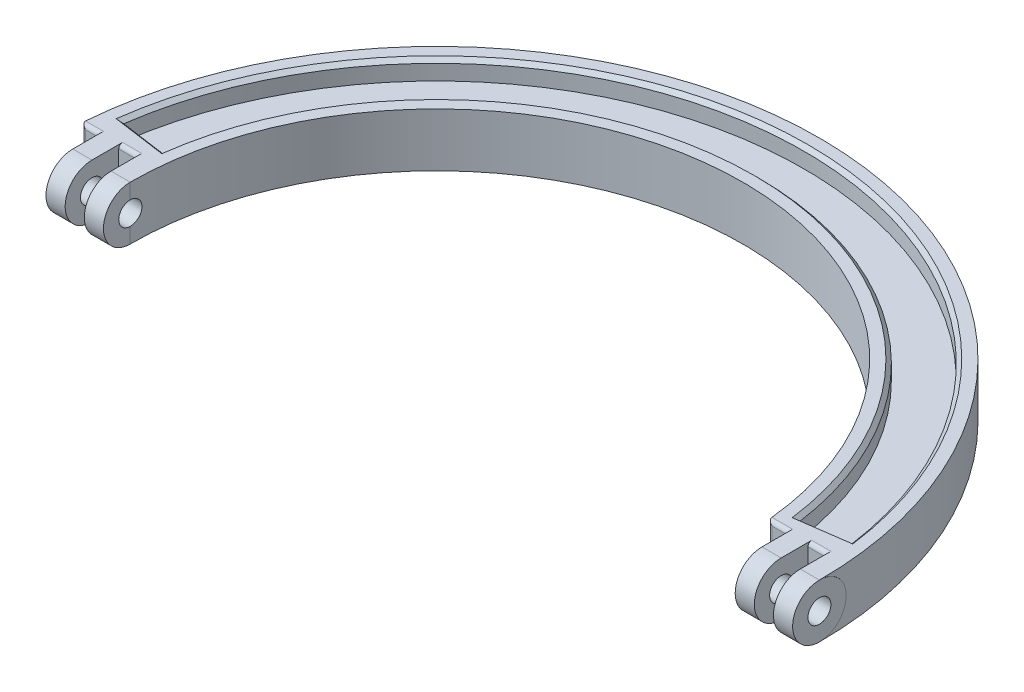
SolidWorks part; units mm, degrees
ref_plane "前视基准面" through (0, 0, 0) normal (0, 0, 1) x (1, 0, 0)
ref_plane "上视基准面" through (0, 0, 0) normal (0, 1, 0) x (1, 0, 0)
ref_plane "右视基准面" through (0, 0, 0) normal (1, 0, 0) x (0, 0, -1)
other "Configuration Table"
sketch "草图2" plane through (0, 0, 0) normal (0, 1, 0) x (1, 0, 0)
  line L0 (-74.0844, 0) -> (74.0844, 0) construction
  line L1 (-50, 0) -> (-40, 0)
  line L2 (40, 0) -> (50, 0)
  arc A0 (50, 0) -> (-50, 0) centre (0, 0) ccw
  arc A1 (40, 0) -> (-40, 0) centre (0, 0) ccw
  point P5 (0, 0)
  dimension "D1" = 40
  dimension "D2" = 50
extrude "凸台-拉伸1" add sketch "草图2" along normal blind 7
sketch "草图3" plane through (0, 7, 0) normal (0, 1, 0) x (1, 0, 0)
  line L0 (0, 0) -> (47.5329, 6.6803) construction
  line L1 (-47.5329, 6.6803) -> (0, 0) construction
  line L2 (41.5913, 5.8453) -> (47.5329, 6.6803)
  line L3 (-47.5329, 6.6803) -> (-41.5913, 5.8453)
  arc A0 (47.5329, 6.6803) -> (-47.5329, 6.6803) centre (0, 0) ccw
  arc A1 (41.5913, 5.8453) -> (-41.5913, 5.8453) centre (0, 0) ccw
  dimension "D2" = 42
  dimension "D1" = 48
sketch "草图5" plane through (0, 0, 0) normal (0, 1, 0) x (1, 0, 0)
  line L0 (0, 0) -> (47.5329, 6.6803) construction
  line L1 (-47.5329, 6.6803) -> (0, 0) construction
  line L2 (41.5913, 5.8453) -> (47.5329, 6.6803)
  line L3 (-47.5329, 6.6803) -> (-41.5913, 5.8453)
  arc A0 (47.5329, 6.6803) -> (-47.5329, 6.6803) centre (0, 0) ccw
  arc A1 (41.5913, 5.8453) -> (-41.5913, 5.8453) centre (0, 0) ccw
  dimension "D2" = 42
  dimension "D1" = 48
extrude "切除-拉伸3" cut sketch "草图3" against normal blind 2.5
extrude "切除-拉伸6" cut sketch "草图5" against normal blind 2.5 and the other way blind 2.5
sketch "草图7" plane through (0, 0, 0) normal (0, 0, 1) x (1, 0, 0)
  point P2 (0, 0)
  point P5 (0, 0)
ref_plane "基准面2" through (-50, 0, 0) normal (-1, 0, 0) x (0, 0, 1)
sketch "草图11" plane through (-50, 0, 0) normal (-1, 0, 0) x (0, 0, 1)
  line L0 (0, 7) -> (0, 0) construction
  circle A0 centre (0, 3.5) radius 3.5
extrude "凸台-拉伸4" add sketch "草图11" against normal blind 10
sketch "草图12" plane through (0, 7, 0) normal (0, 1, 0) x (1, 0, 0)
  line L0 (-50, 3.85) -> (-50, -3.85) construction
  line L1 (-50, 3.5) -> (-47.5, 3.5)
  line L2 (-50, 3.5) -> (-50, -5.3034)
  line L3 (-50, -5.3034) -> (-47.5, -5.3034)
  line L4 (-47.5, 3.5) -> (-47.5, -5.3034)
  line L5 (-50, 0) -> (-40, 0) construction
  line L6 (-45, 3.5) -> (-42.5, 3.5)
  line L7 (-45, 3.5) -> (-45, -5.3034)
  line L8 (-45, -5.3034) -> (-42.5, -5.3034)
  line L9 (-42.5, 3.5) -> (-42.5, -5.3034)
  line L10 (40, 0) -> (50, 0) construction
  line L11 (39.8466, 3.5) -> (42.5, 3.5)
  line L12 (39.8466, 3.5) -> (39.8466, -5.0196)
  line L13 (39.8466, -5.0196) -> (42.5, -5.0196)
  line L14 (42.5, 3.5) -> (42.5, -5.0196)
  line L15 (45, 3.5) -> (47.5, 3.5)
  line L16 (45, 3.5) -> (45, -5.0196)
  line L17 (45, -5.0196) -> (47.5, -5.0196)
  line L18 (47.5, 3.5) -> (47.5, -5.0196)
  arc A0 (40, 0) -> (-40, 0) centre (0, 0) ccw construction
  dimension "D1" = 3.5
  dimension "D2" = 2.5
  dimension "D3" = 2.5
  dimension "D4" = 2.5
  dimension "D5" = 3.5
  dimension "D6" = 2.5
  dimension "D7" = 2.5
  dimension "D8" = 2.5
ref_plane "基准面4" through (50, 0, 0) normal (1, 0, 0) x (0, 0, -1)
sketch "草图13" plane through (50, 0, 0) normal (1, 0, 0) x (0, 0, -1)
  line L0 (0, 7) -> (0, 0) construction
  circle A0 centre (0, 3.5) radius 3.5
extrude "凸台-拉伸5" add sketch "草图13" against normal blind 10
extrude "切除-拉伸10" cut sketch "草图12" against normal blind 10
chamfer "倒角1" distance 0.5 4 edges at (44.5621, 7, -6.2628) (0, 7, -42) (0, 7, -48) (-44.5621, 7, -6.2628)
chamfer "倒角2" distance 0.5 angle 45 4 edges at (44.5621, 0, -6.2628) (0, 0, -48) (-44.5621, 0, -6.2628) (0, 0, -42)
fillet "圆角1" radius 0.5 10 edges at (-49.8773, 3.5, -3.5) (-48.6887, 0, -3.5) (-48.6887, 7, -3.5) (-43.75, 7, -3.5) (-43.75, 0, -3.5) (46.25, 7, -3.5) (46.25, 0, -3.5) (41.1733, 7, -3.5) (41.1733, 0, -3.5) (39.8466, 3.5, -3.5)
sketch "草图14" plane through (50, 0, 0) normal (1, 0, 0) x (0, 0, -1)
  circle A0 centre (0, 3.5) radius 1.5
  arc A1 (0, 7) -> (0, 0) centre (0, 3.5) ccw construction
  point P2 (0, 0)
extrude "切除-拉伸11" cut sketch "草图14" against normal blind 123
